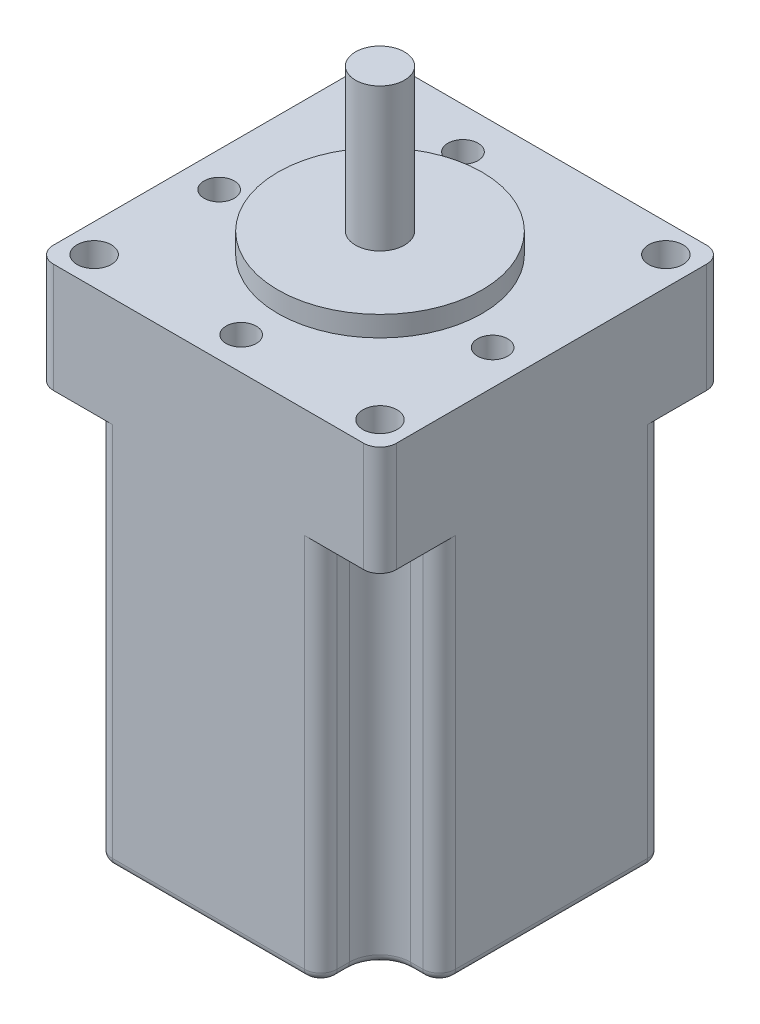
SolidWorks part; units mm, degrees
material "PBT General Purpose"
ref_plane "Front Plane" through (0, 0, 0) normal (0, 0, 1) x (1, 0, 0)
ref_plane "Top Plane" through (0, 0, 0) normal (0, 1, 0) x (1, 0, 0)
ref_plane "Right Plane" through (0, 0, 0) normal (1, 0, 0) x (0, 0, -1)
sketch "Sketch1" plane through (0, 0, 0) normal (0, 1, 0) x (1, 0, 0)
  line L1 (-21, -21) -> (21, -21)
  line L2 (-21, -21) -> (-21, 21)
  line L3 (-21, 21) -> (21, 21)
  line L4 (21, -21) -> (21, 21)
  line L5 (-21, -21) -> (21, 21) construction
  line L6 (-21, 21) -> (21, -21) construction
  point P0 (0, 0)
  dimension "D1" = 42
  dimension "D2" = 42
extrude "Boss-Extrude1" add sketch "Sketch1" against normal blind 60.4
sketch "Sketch2" plane through (0, 0, 0) normal (0, 1, 0) x (1, 0, 0)
  circle A0 centre (0, 0) radius 12.5
  dimension "D1" = 25
extrude "Boss-Extrude2" add sketch "Sketch2" along normal blind 2.5
sketch "Sketch4" plane through (0, 0, 0) normal (0, 1, 0) x (1, 0, 0)
  circle A0 centre (0, 0) radius 3
  dimension "D1" = 6
extrude "Boss-Extrude3" add sketch "Sketch4" along normal blind 20
sketch "Sketch5" plane through (0, -60.4, 0) normal (0, -1, 0) x (1, 0, 0)
  line L0 (21, 21) -> (21, -21) construction
  line L1 (-21, 21) -> (21, 21) construction
  line L2 (21, 21) -> (21, 13.75)
  line L3 (13.75, 21) -> (21, 21)
  line L4 (13.75, 17.5) -> (13.75, 21)
  line L5 (17.5, 13.75) -> (21, 13.75)
  arc A0 (13.75, 17.5) -> (17.5, 13.75) centre (17.5, 17.5) ccw
  dimension "D3" = 7.5
  dimension "D1" = 17.5
  dimension "D2" = 17.5
extrude "Cut-Extrude1" cut sketch "Sketch5" against normal blind 47
hole_wizard "Ø4.2 (4.2) Diameter Hole1" positions "Sketch6" profile "Sketch7" hole size "Ø4.2" standard "ANSI Metric" end condition up to next
sketch "Sketch6" plane through (0, 0, 0) normal (0, 1, 0) x (1, 0, 0)
  point P0 (17.5, -17.5)
  dimension "D1" = 17.5
  dimension "D2" = 17.5
sketch "Sketch7" plane through (17.5, 0, 17.5) normal (1, 0, 0) x (0, 0, 1)
  line L0 (0, 0) -> (0, 13.401)
  line L1 (0, 13.401) -> (2.1, 13.401)
  line L2 (2.1, 13.401) -> (2.1, 0)
  line L5 (2.1, 0) -> (0, 0)
  line L11 (0, -6.35) -> (0, 107.95) construction
  dimension "Thru Hole Dia." = 4.2
  dimension "Thru Hole Depth" = 13.401
ref_axis "Axis1" through (0, 20, 0) along (0, -1, 0)
pattern_circular "CirPattern1" count 4 over 360 about axis through (0, 20, 0) along (0, -1, 0) of "Cut-Extrude1", "Ø4.2 (4.2) Diameter Hole1"
sketch "Sketch8" plane through (0, 0, 0) normal (0, 1, 0) x (1, 0, 0)
  line L0 (0, 0) -> (0, 17) construction
  line L1 (0, 0) -> (-5.8143, 15.9748) construction
  line L2 (0, 0) -> (-16.7417, -2.952) construction
  line L3 (0, 0) -> (0, -17) construction
  line L4 (0, 0) -> (16.7417, -2.952) construction
  circle A0 centre (0, 0) radius 17 construction
  point P9 (-5.8143, 15.9748)
  point P10 (-16.7417, -2.952)
  point P11 (0, -17)
  point P12 (16.7417, -2.952)
  dimension "D1" = 34
  dimension "D2" = 20
  dimension "D3" = 80
  dimension "D4" = 80
  dimension "D5" = 80
hole_wizard "Ø3.7 (3.7) Diameter Hole1" positions "Sketch9" profile "Sketch11" hole size "Ø3.7" standard "ANSI Metric"
sketch "Sketch9" plane through (0, 0, 0) normal (0, 1, 0) x (1, 0, 0)
  point P0 (-5.8143, 15.9748)
  point P3 (-16.7417, -2.952)
  point P6 (0, -17)
  point P9 (16.7417, -2.952)
sketch "Sketch11" plane through (-5.8143, 0, -15.9748) normal (1, 0, 0) x (0, 0, 1)
  line L0 (0, 0) -> (0, 7.1116)
  line L1 (0, 7.1116) -> (1.85, 6)
  line L2 (1.85, 6) -> (1.85, 0)
  line L5 (1.85, 0) -> (0, 0)
  line L10 (0, 7.1116) -> (-1.85, 6) construction
  line L11 (0, -6.35) -> (0, 107.95) construction
  dimension "Hole Dia." = 3.7
  dimension "Hole Depth" = 6
  dimension "Drill Angle" = 118
fillet "Fillet1" radius 2 12 edges at (13.75, -36.9, 21) (-13.75, -36.9, 21) (-21, -6.7, 21) (-21, -6.7, -21) (21, -6.7, -21) (21, -6.7, 21) (21, -36.9, 13.75) (21, -36.9, -13.75) (13.75, -36.9, -21) (-13.75, -36.9, -21) (-21, -36.9, 13.75) (-21, -36.9, -13.75)
fillet "Fillet2" radius 1 24 edges at (14.8483, -60.4, 14.8483) (18.25, -60.4, 13.75) (20.4142, -60.4, 13.1642) (21, -60.4, 0) (20.4142, -60.4, -13.1642) (18.25, -60.4, -13.75) (14.8483, -60.4, -14.8483) (13.75, -60.4, -18.25) (13.1642, -60.4, -20.4142) (0, -60.4, -21) (-13.1642, -60.4, -20.4142) (-13.75, -60.4, -18.25) (-14.8483, -60.4, -14.8483) (-18.25, -60.4, -13.75) (-20.4142, -60.4, -13.1642) (-21, -60.4, 0) (-20.4142, -60.4, 13.1642) (-18.25, -60.4, 13.75) (-14.8483, -60.4, 14.8483) (-13.75, -60.4, 18.25) (-13.1642, -60.4, 20.4142) (0, -60.4, 21) (13.1642, -60.4, 20.4142) (13.75, -60.4, 18.25)
move or copy body "Body-Move/Copy1" [suppressed] bodies to move or copy 108
